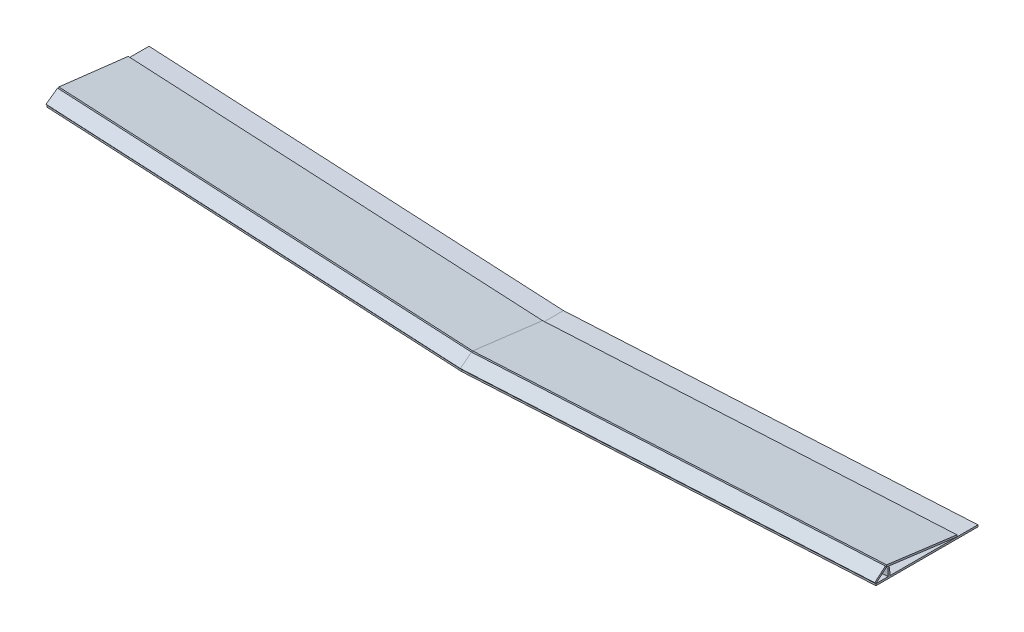
SolidWorks part; units mm, degrees
ref_plane "Front Plane" through (0, 0, 0) normal (0, 0, 1) x (1, 0, 0)
ref_plane "Top Plane" through (0, 0, 0) normal (0, 1, 0) x (1, 0, 0)
ref_plane "Right Plane" through (0, 0, 0) normal (1, 0, 0) x (0, 0, -1)
ref_axis "Axis1" through (0, 0, 10.3085) along (0, 0, -1)
ref_plane "Plane3" through (0, 0, 0) normal (0.9986, 0.0523, 0) x (0, 0, -1)
sketch "Sketch1" plane through (0, 0, 0) normal (0.9986, 0.0523, 0) x (0, 0, -1)
  line L0 (-10.3085, 0) -> (133.5385, 0) construction
  line L1 (0, 0) -> (184.15, 0)
  line L2 (0, 0) -> (0, 3.175)
  line L3 (0, 3.175) -> (184.15, 3.175)
  line L4 (184.15, 0) -> (184.15, 3.175)
  line L5 (0, 3.175) -> (20.0163, 18.8117)
  line L6 (0, 3.175) -> (-1.9546, 5.677)
  line L7 (20.0163, 18.8117) -> (18.0617, 21.3138)
  line L8 (-1.9546, 5.677) -> (18.0617, 21.3138)
  line L9 (20.0163, 18.8117) -> (146.05, 3.175)
  line L10 (20.0163, 18.8117) -> (20.4072, 21.9626)
  line L11 (146.05, 3.175) -> (146.4409, 6.3258)
  line L12 (20.4072, 21.9626) -> (146.4409, 6.3258)
  line L13 (22.225, 3.175) -> (25.4, 3.175)
  line L14 (22.225, 3.175) -> (22.225, 15.875)
  line L15 (25.4, 3.175) -> (25.4, 15.875)
  line L16 (22.225, 15.875) -> (25.4, 15.875)
  dimension "D1" = 3.175
  dimension "D2" = 3.175
  dimension "D3" = 3.175
  dimension "D4" = 25.4
  dimension "D5" = 127
  dimension "D6" = 146.05
  dimension "D7" = 184.15
  dimension "D8" = 12.7
  dimension "D9" = 22.225
  dimension "D10" = 3.175
extrude "Boss-Extrude4" add sketch "Sketch1" along normal blind 749.3 contours L5 L14 L7 L8 L6 | L10 L16 L15 L9 L11 L12 | L1 L4 L3 L2 | L3 L15 L9 L5 L14 | L16 L10 L9 L15 | L14 L5 L7 | L2 L1 L4 L3 | L5 L6 L8 L7 | L9 L10 L12 L11 region at (-0.0831, 1.5853, -92.075) region at (-0.6408, 12.2276, -9.0309) region at (-0.4985, 9.5119, -23.8125) region at (-0.6578, 12.5516, -83.2286)
extrude "Boss-Extrude6" add sketch "Sketch1<3>" along normal blind 749.3 separate body contours L3 L15 L9 L5 L14 | L15 L16 L14 L13 region at (-0.4985, 9.5119, -23.8125)
sketch "Sketch1<3>" plane through (0, 0, 0) normal (0.9986, 0.0523, 0) x (0, 0, -1) same geometry as "Sketch1"
mirror "Mirror5" about plane through (0, 0, 0) normal (1, 0, 0) of bodies 141 134 135 142 132 133
